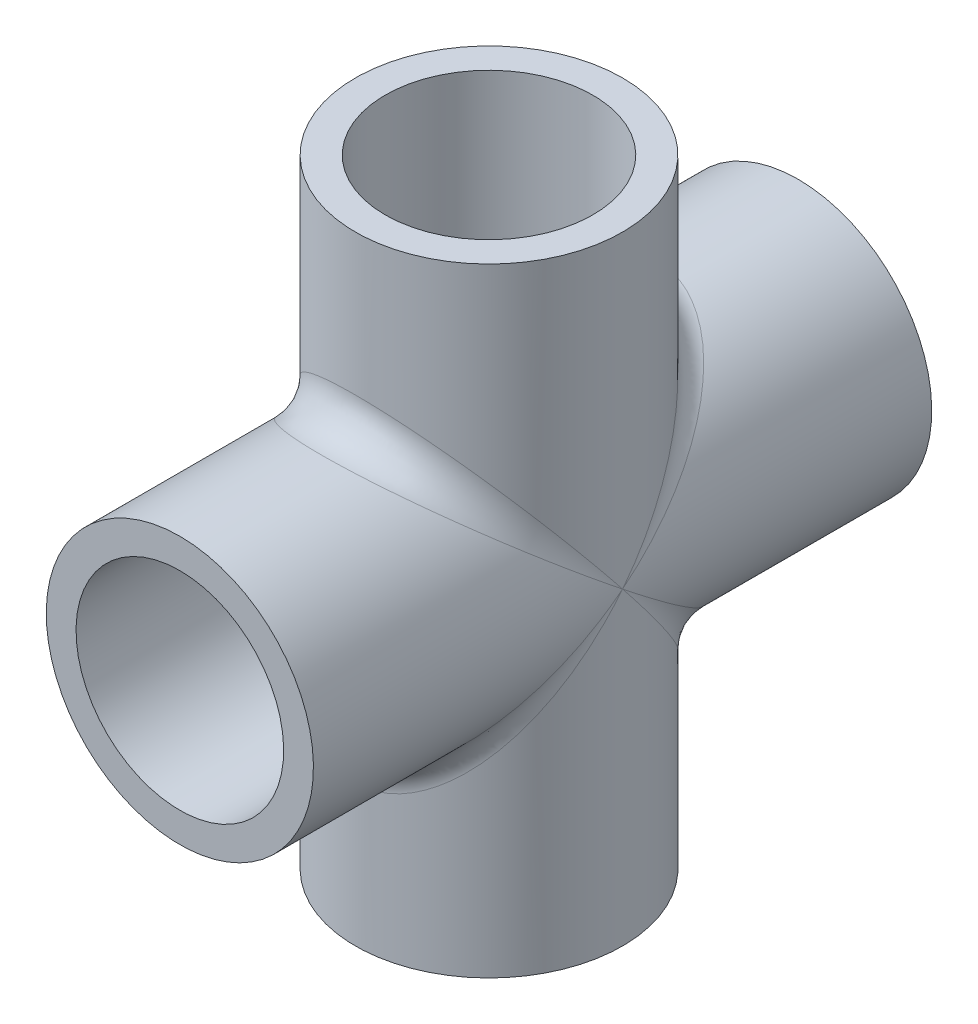
SolidWorks part; units mm, degrees
ref_plane "Front Plane" through (0, 0, 0) normal (0, 0, 1) x (1, 0, 0)
ref_plane "Top Plane" through (0, 0, 0) normal (0, 1, 0) x (1, 0, 0)
ref_plane "Right Plane" through (0, 0, 0) normal (1, 0, 0) x (0, 0, -1)
sketch "Sketch1" plane through (0, 0, 0) normal (1, 0, 0) x (0, 0, -1)
  line L0 (0, 0) -> (-32.1469, 0) construction
  line L1 (0, 0) -> (32.1469, 0) construction
  line L2 (0, 0) -> (0, 32.1469) construction
  line L3 (-13.4937, -7.8994) -> (-13.4938, 7.8994) construction
  line L4 (-7.8994, 13.4937) -> (7.8994, 13.4937) construction
  line L5 (13.4937, -7.8994) -> (13.4937, 7.8994) construction
  line L6 (-32.1469, -13.8906) -> (-32.1469, 13.8906) construction
  line L7 (32.1469, -13.8906) -> (32.1469, 13.8906) construction
  line L8 (13.8906, 32.1469) -> (-13.8906, 32.1469) construction
  line L9 (-13.4938, 7.8994) -> (-32.1469, 7.8994) construction
  line L10 (-7.8994, 13.4937) -> (-7.8994, 32.1469) construction
  line L11 (13.4937, 7.8994) -> (32.1469, 7.8994) construction
  line L12 (-22.8203, -10.795) -> (-22.8203, 10.795) construction
  line L13 (-10.795, 22.8203) -> (10.795, 22.8203) construction
  line L14 (22.8203, -10.795) -> (22.8203, 10.795) construction
  line L15 (0, 0) -> (0, -32.1469) construction
  line L16 (-13.8906, -32.1469) -> (13.8906, -32.1469) construction
  line L17 (-7.8994, -13.4938) -> (7.8994, -13.4937) construction
  line L18 (-10.795, -22.8203) -> (10.795, -22.8203) construction
  line L19 (7.8994, -13.4937) -> (7.8994, -32.1469) construction
  point P4 (0, 0)
  point P10 (-13.4937, 0)
  point P13 (0, 13.4937)
  point P16 (13.4937, 0)
  point P19 (-32.1469, 0)
  point P22 (32.1469, 0)
  point P25 (0, 32.1469)
  point P27 (-22.8203, 7.8994)
  point P31 (-22.8203, 0)
  point P34 (0, 22.8203)
  point P37 (22.8203, 0)
  point P38 (-7.8994, 22.8203)
  point P39 (22.8203, 7.8994)
  point P42 (0, -32.1469)
  point P46 (0, -13.4937)
  point P49 (0, -22.8203)
  point P50 (7.8994, -22.8203)
  dimension "Horz Leg Length" = 32.1469
  dimension "Vert Leg Length" = 32.1469
  dimension "Horz Length" = 64.2938
  dimension "Horz Center to Socket" = 13.4937
  dimension "D1" = 13.4937
  dimension "Vert Center to Socket" = 13.4937
  dimension "Pipe ID" = 15.7988
  dimension "Tee OD" = 27.7812
  dimension "For Pipe OD" = 21.59
  dimension "D2" = 13.4937
  dimension "Vert Length" = 64.2938
sketch "Sketch2" plane through (0, 0, 0) normal (1, 0, 0) x (0, 0, -1)
  line L0 (-32.1469, 13.8906) -> (32.1469, 13.8906)
  line L1 (32.1469, 13.8906) -> (32.1469, 0)
  line L2 (32.1469, -13.8906) -> (32.1469, 13.8906) construction
  line L8 (-32.1469, -13.8906) -> (-32.1469, 13.8906) construction
  line L9 (-32.1469, 0) -> (-32.1469, 13.8906)
  line L10 (-32.1469, 0) -> (32.1469, 0)
revolve "Revolve1" add sketch "Sketch2" angle 360 about L0
sketch "Sketch3" plane through (0, 0, 0) normal (1, 0, 0) x (0, 0, -1)
  line L0 (0, 32.1469) -> (13.8906, 32.1469)
  line L1 (13.8906, 32.1469) -> (13.8906, -32.1469)
  line L3 (13.8906, -32.1469) -> (0, -32.1469)
  line L4 (0, -32.1469) -> (0, 32.1469)
revolve "Revolve2" add sketch "Sketch3" angle 360 about L2
sketch "Sketch4" plane through (0, 0, 0) normal (1, 0, 0) x (0, 0, -1)
  line L0 (-32.1469, 10.795) -> (-13.4938, 10.795)
  line L1 (-32.1469, -13.8906) -> (-32.1469, 13.8906) construction
  line L2 (-13.4938, 10.795) -> (-13.4938, 7.8994)
  line L3 (-13.4938, 7.8994) -> (13.4937, 7.8994)
  line L4 (13.4937, 7.8994) -> (13.4937, 10.795)
  line L5 (13.4937, 10.795) -> (32.1469, 10.795)
  line L6 (32.1469, -13.8906) -> (32.1469, 13.8906) construction
  line L7 (32.1469, 10.795) -> (32.1469, 0)
  line L8 (32.1469, 0) -> (-32.1469, 0)
  line L9 (-32.1469, 0) -> (-32.1469, 10.795)
revolve "Cut-Revolve1" cut sketch "Sketch4" angle 360 about L8
sketch "Sketch5" plane through (0, 0, 0) normal (1, 0, 0) x (0, 0, -1)
  line L0 (0, 32.1469) -> (0, -32.1469)
  line L1 (13.8906, 32.1469) -> (-13.8906, 32.1469) construction
  line L3 (0, -32.1469) -> (-10.795, -32.1469)
  line L5 (-7.8994, -13.4938) -> (-7.8994, 13.4937)
  line L6 (-7.8994, 13.4937) -> (-10.795, 13.4937)
  line L7 (-10.795, 13.4937) -> (-10.795, 32.1469)
  line L8 (-10.795, 32.1469) -> (0, 32.1469)
  line L9 (-13.8906, -32.1469) -> (13.8906, -32.1469) construction
  line L10 (-10.795, -32.1469) -> (-10.795, -13.4938)
  line L11 (-10.795, -13.4938) -> (-7.8994, -13.4938)
revolve "Cut-Revolve2" cut sketch "Sketch5" angle 360 about L0
fillet "Fillet1" radius 3.5847 4 edges at (0, -13.8906, -13.8906) (0, -13.8906, 13.8906) (0, 13.8906, 13.8906) (0, 13.8906, -13.8906)
sketch "Sketch6" plane through (0, 0, 0) normal (1, 0, 0) x (0, 0, -1)
  line L0 (-32.1469, 10.795) -> (-13.4938, 10.795)
  line L1 (-32.1469, -13.8906) -> (-32.1469, 13.8906) construction
  line L2 (-13.4938, 10.795) -> (-13.4938, 7.8994)
  line L3 (-13.4938, 7.8994) -> (-7.8994, 7.8994)
  line L4 (-7.8994, 7.8994) -> (-7.8994, 13.4937)
  line L5 (-7.8994, 13.4937) -> (-10.795, 13.4937)
  line L6 (-10.795, 13.4937) -> (-10.795, 32.1469)
  line L7 (13.8906, 32.1469) -> (-13.8906, 32.1469) construction
  line L8 (-13.4937, -7.8994) -> (-7.8994, -7.8994)
  line L9 (13.4937, -7.8994) -> (13.4937, -10.795)
  line L10 (13.4937, -10.795) -> (32.1469, -10.795)
  line L11 (32.1469, -13.8906) -> (32.1469, 13.8906) construction
  line L12 (-13.4937, -7.8994) -> (-13.4937, -10.795)
  line L13 (-13.4937, -10.795) -> (-32.1469, -10.795)
  line L14 (32.1469, 10.795) -> (13.4937, 10.795)
  line L15 (13.4937, 10.795) -> (13.4937, 7.8994)
  line L16 (13.4937, 7.8994) -> (7.8994, 7.8994)
  line L17 (7.8994, 7.8994) -> (7.8994, 13.4937)
  line L18 (7.8994, 13.4937) -> (10.795, 13.4938)
  line L19 (10.795, 13.4938) -> (10.795, 32.1469)
  line L20 (-7.8994, -13.4938) -> (-7.8994, -7.8994)
  line L21 (7.8994, -13.4937) -> (7.8994, -7.8994)
  line L22 (10.795, -32.1469) -> (10.795, -13.4937)
  line L23 (-13.8906, -32.1469) -> (13.8906, -32.1469) construction
  line L24 (10.795, -13.4937) -> (7.8994, -13.4937)
  line L25 (-10.795, -32.1469) -> (-10.795, -13.4938)
  line L26 (-10.795, -13.4938) -> (-7.8994, -13.4938)
  line L27 (7.8994, -7.8994) -> (13.4937, -7.8994)
sketch "Sketch7" plane through (0, 0, 32.1469) normal (0, 0, 1) x (1, 0, 0)
  circle A0 centre (0, 0) radius 10.795 construction
  circle A1 centre (0, 0) radius 10.795
  point P3 (0, -10.795)
  point P4 (10.795, 0)
  point P5 (-10.795, 0)
  point P6 (0, 10.795)
equation "\"D1@Fillet1\"=\"Tee OD@Sketch1\"*0.1290322581"
equation "\"D2@Sketch1\"=\"Vert Center to Socket@Sketch1\""
equation "\"Horz Leg Length@Sketch1\" = \"Horz Length@Sketch1\" / 2"
equation "\"Vert Leg Length@Sketch1\"=\"Vert Length@Sketch1\"/2"
equation "\"D1@Sketch1\"=\"Horz Center to Socket@Sketch1\""
